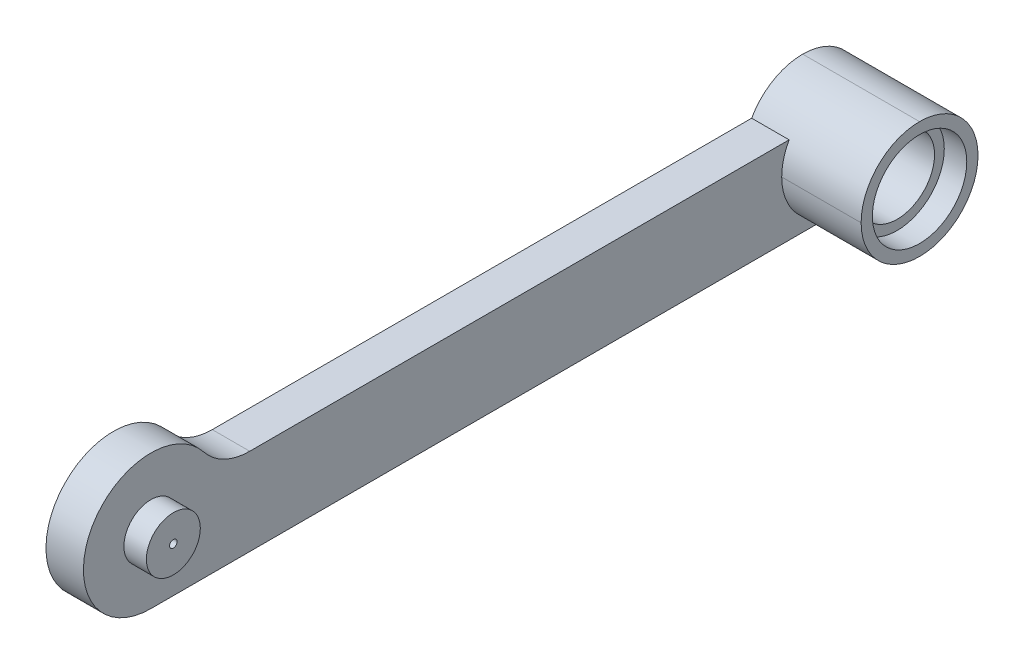
SolidWorks part; units mm, degrees
ref_plane "前视基准面" through (0, 0, 0) normal (0, 0, 1) x (1, 0, 0)
ref_plane "上视基准面" through (0, 0, 0) normal (0, 1, 0) x (1, 0, 0)
ref_plane "右视基准面" through (0, 0, 0) normal (1, 0, 0) x (0, 0, -1)
other "Configuration Table"
sketch "草图1" plane through (0, 0, 0) normal (1, 0, 0) x (0, 0, -1)
  line L0 (46, 3.3) -> (46, -4.5) construction
  line L1 (0, -4.5) -> (49.9, -4.5)
  line L2 (0, -4.5) -> (0, 3.3)
  line L3 (0, 3.3) -> (49.9, 3.3)
  line L4 (49.9, -4.5) -> (49.9, 3.3)
  line L6 (42.1, -4.5) -> (49.9, -4.5)
  line L7 (42.1, -4.5) -> (42.1, 3.3)
  line L8 (42.1, 3.3) -> (49.9, 3.3)
  line L9 (49.9, -4.5) -> (49.9, 3.3)
  line L10 (42.1, -4.5) -> (49.9, 3.3) construction
  line L11 (42.1, 3.3) -> (49.9, -4.5) construction
  circle A4 centre (0, 0) radius 1.8
  circle A5 centre (0, 0) radius 4.5
  circle A6 centre (46, -0.6) radius 2.5
  circle A7 centre (46, -0.6) radius 3.15
  circle A8 centre (0, 0) radius 0.25
  point P9 (46, -0.6)
  dimension "D1" = 3.6
  dimension "D4" = 46
  dimension "D5" = 3.9
  dimension "D2" = 9
  dimension "D6" = 5
  dimension "D7" = 6.3
  dimension "D8" = 0.5
  dimension "D3" = 7.8
extrude "凸台-拉伸1" add sketch "草图1" along normal blind 2.5 contours A5 | L3 L4 L1 L2
extrude "凸台-拉伸3" add sketch "草图1<6>" along normal blind 1.5 from surface contours L2 A4 | L2 A4 region at (0, 0, 0.7769) region at (0, 0, -0.7769) starting at face at (2.5, -0.0392, -24.2851)
sketch "草图1<6>" plane through (0, 0, 0) normal (1, 0, 0) x (0, 0, -1) same geometry as "草图1"
extrude "凸台-拉伸2" add sketch "草图1<5>" along normal blind 7.8 contours A6 | A7 A6 | L7 L1 L4 L3 A7 region at (0, -0.6, -42.2103) region at (0, -0.6, -46) region at (0, -0.6, -42.9391)
sketch "草图1<5>" plane through (0, 0, 0) normal (1, 0, 0) x (0, 0, -1) same geometry as "草图1"
extrude "切除-拉伸1" cut sketch "草图1<7>" along normal through all contours A6 region at (0, -0.6, -46)
sketch "草图1<7>" plane through (0, 0, 0) normal (1, 0, 0) x (0, 0, -1) same geometry as "草图1"
extrude "切除-拉伸2" cut sketch "草图1<8>" along normal blind 1.5 contours A7 A6 region at (0, -0.6, -42.9391)
sketch "草图1<8>" plane through (0, 0, 0) normal (1, 0, 0) x (0, 0, -1) same geometry as "草图1"
extrude "切除-拉伸3" cut sketch "草图1<9>" against normal blind 1.5 from surface contours A7 A6 region at (0, -0.6, -42.9391) starting at face at (7.8, -0.6, -48.5)
sketch "草图1<9>" plane through (0, 0, 0) normal (1, 0, 0) x (0, 0, -1) same geometry as "草图1"
sketch "草图2" plane through (0, 0, 0) normal (-1, 0, 0) x (0, 0, 1)
  line L0 (-3.0594, 3.3) -> (-49.9, 3.3) construction
  line L1 (-42.1, 3.3) -> (-4.5, 3.3)
  line L2 (-42.1, 3.3) -> (-42.1, 1.3)
  line L3 (-42.1, 1.3) -> (-4.5, 1.3)
  line L4 (-4.5, 3.3) -> (-4.5, 1.3)
  line L5 (-42.1, 3.3) -> (-42.1, -4.5) construction
  line L6 (-4.5, 3.3) -> (-3.0594, 3.3)
  line L8 (-4.5, 1.3) -> (-4.3081, 1.3)
  line L9 (-4.5, 1.3) -> (-4.5, 3.3)
  line L10 (-4.5, 3.3) -> (-4.3081, 3.3)
  line L11 (-4.3081, 1.3) -> (-4.3081, 3.3)
  arc A1 (0, -4.5) -> (-3.0594, 3.3) centre (0, 0) ccw construction
  circle A2 centre (0, 0) radius 4.5
  line M7 (-3.0594, 3.3) -> (-49.9, 3.3)
  dimension "D1" = 2
extrude "切除-拉伸4" cut sketch "草图2" against normal through all contours A2 L11 M7 | L8 L11 L6 L4 | L4 L2 L3 M7 region at (0, 2.3, -23.3) region at (0, 2.3, -4.4041) region at (0, 2.7076, -3.9302)
fillet "圆角1" radius 3.9 5 edges at (3.9, -4.5, -49.9) (3.9, 3.3, -49.9) (5.15, -4.5, -42.1) (3.9, 3.3, -42.1) (1.25, 1.3, -4.3081)
ref_plane "基准面1" through (0, -10, 0) normal (0, 1, 0) x (1, 0, 0)
mirror "镜向2" about plane through (0, -10, 0) normal (0, 1, 0) of bodies 118 114
sketch "草图3" plane through (2.5, 0, 0) normal (1, 0, 0) x (0, 0, -1)
  line L1 (-11.0856, -9.8093) -> (53.6185, -9.8093)
  line L2 (-11.0856, -9.8093) -> (-11.0856, -30.7557)
  line L3 (-11.0856, -30.7557) -> (53.6185, -30.7557)
  line L4 (53.6185, -9.8093) -> (53.6185, -30.7557)
extrude "切除-拉伸5" cut sketch "草图3" against normal through all and the other way through all
